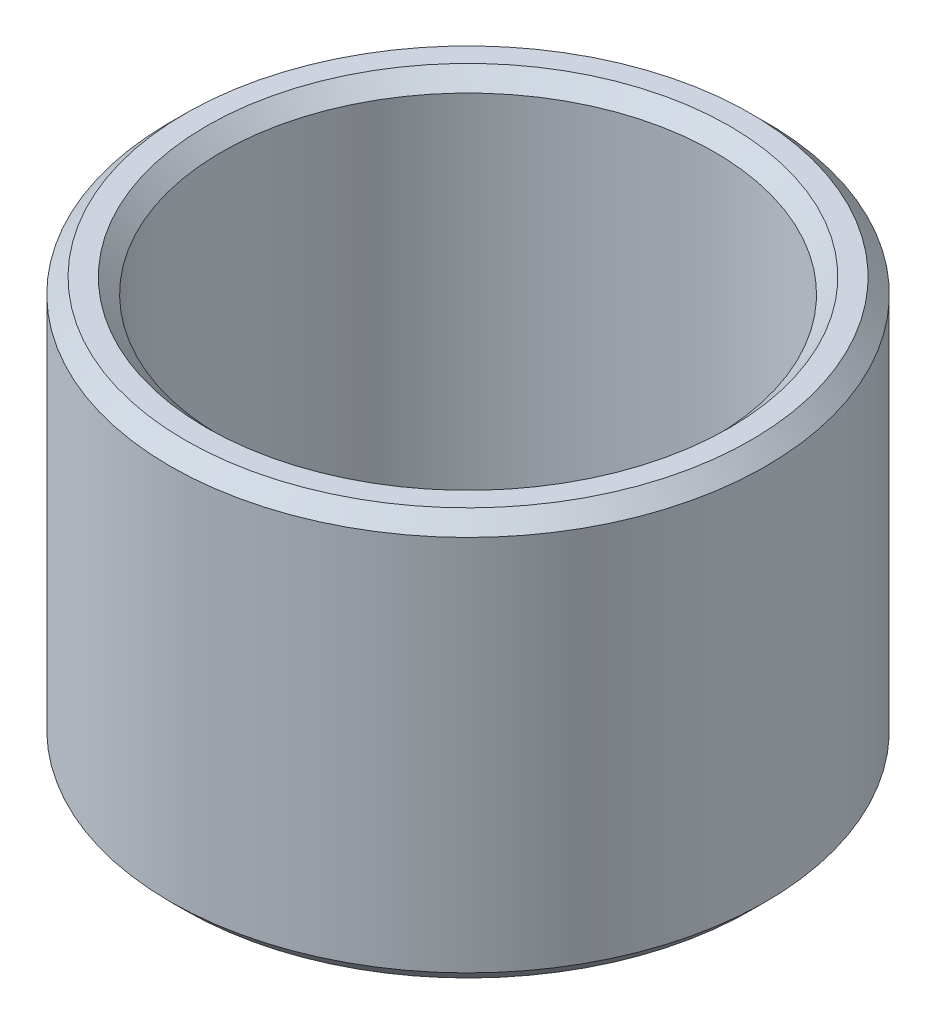
SolidWorks part; units mm, degrees
ref_plane "Front Plane" through (0, 0, 0) normal (0, 0, 1) x (1, 0, 0)
ref_plane "Top Plane" through (0, 0, 0) normal (0, 1, 0) x (1, 0, 0)
ref_plane "Right Plane" through (0, 0, 0) normal (1, 0, 0) x (0, 0, -1)
sketch "Sketch1" plane through (0, 0, 0) normal (0, 1, 0) x (1, 0, 0)
  circle A0 centre (0, 0) radius 40
  dimension "SLEEVE_OD" = 80
extrude "Boss-Extrude1" add sketch "Sketch1" along normal blind 54.6708
sketch "Sketch2" plane through (0, 0, 0) normal (0, 1, 0) x (1, 0, 0)
  circle A0 centre (0, 0) radius 33.0884
  dimension "BORE_D" = 66.1767
extrude "Cut-Extrude1" cut sketch "Sketch2" along normal through all
chamfer "Chamfer1" distance 2.0179 angle 45 4 edges at (0, 54.6708, 33.0884) (0, 0, 33.0884) (0, 0, 40) (0, 54.6708, 40)
